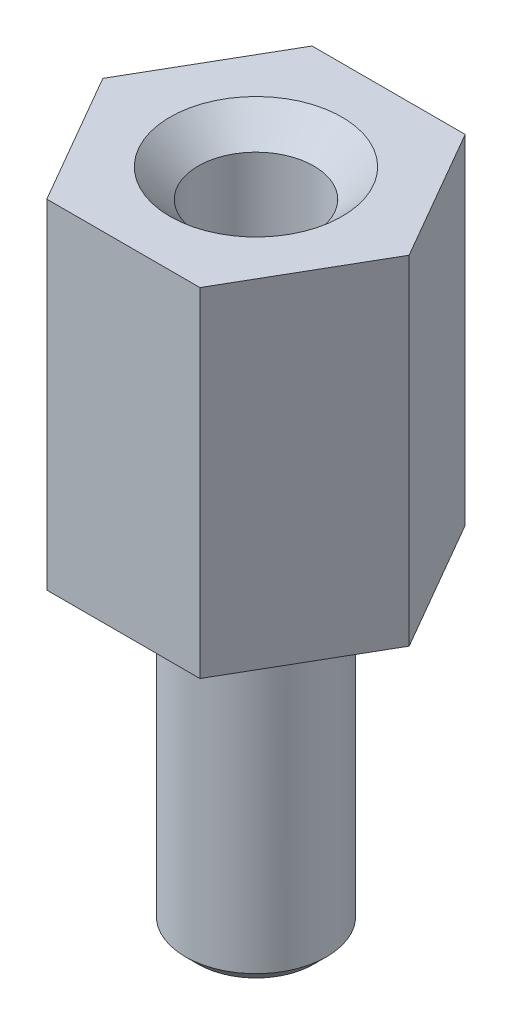
SolidWorks part; units mm, degrees
ref_plane "Front Plane" through (0, 0, 0) normal (0, 0, 1) x (1, 0, 0)
ref_plane "Top Plane" through (0, 0, 0) normal (0, 1, 0) x (1, 0, 0)
ref_plane "Right Plane" through (0, 0, 0) normal (1, 0, 0) x (0, 0, -1)
ref_plane "Plane1" through (0, 6, 0) normal (0, 1, 0) x (1, 0, 0)
sketch "Sketch1" plane through (0, 6, 0) normal (0, 1, 0) x (1, 0, 0)
  line L0 (1.3568, -2.35) -> (2.7135, 0)
  line L1 (2.7135, 0) -> (1.3568, 2.35)
  line L2 (1.3568, 2.35) -> (-1.3568, 2.35)
  line L3 (-1.3568, 2.35) -> (-2.7135, 0)
  line L4 (-2.7135, 0) -> (-1.3568, -2.35)
  line L5 (-1.3568, -2.35) -> (1.3568, -2.35)
  circle A0 centre (0, 0) radius 2.7135 construction
  dimension "D1" = 4.7
extrude "Boss-Extrude1" add sketch "Sketch1" against normal blind 6
ref_plane "Plane2" through (0, 0, 0) normal (0, 0, -1) x (-1, 0, 0)
sketch "Sketch2" plane through (0, 0, 0) normal (0, 0, -1) x (-1, 0, 0)
  line L0 (-1.25, -6) -> (0, -6)
  line L1 (0, -6) -> (0, 0)
  line L2 (0, 0) -> (-1.25, 0)
  line L3 (-1.25, 0) -> (-1.25, -6)
  line L4 (0, -6) -> (0, 0) construction
  line L5 (0, 0) -> (1.25, 0) construction
  dimension "D1" = 6
  dimension "D2" = 2.5
revolve "Revolve1" add sketch "Sketch2" angle 360 about L4 reverse direction yes
hole_wizard "Tap Drill for M2.5x0.45 Tap1" positions "Sketch4" profile "Sketch3" hole size "M2.5x0.45" standard "ANSI Metric"
sketch "Sketch4" plane through (0, 6, 0) normal (0, 1, 0) x (1, 0, 0)
  point P0 (0, 0)
sketch "Sketch3" plane through (0, 6, 0) normal (1, 0, 0) x (0, 0, 1)
  line L0 (0, 0) -> (0, 19)
  line L1 (0, 19) -> (1.025, 19)
  line L2 (1.025, 19) -> (1.025, 0)
  line L5 (1.025, 0) -> (0, 0)
  line L10 (0, 19) -> (-1.025, 19) construction
  line L11 (0, -6.35) -> (0, 107.95) construction
  dimension "Hole Dia." = 2.05
  dimension "Hole Depth" = 19
  dimension "Drill Angle" = 180
chamfer "Chamfer1" distance 0.5 angle 45 2 edges at (0, -6, 1.25) (0, 6, 1.025)
